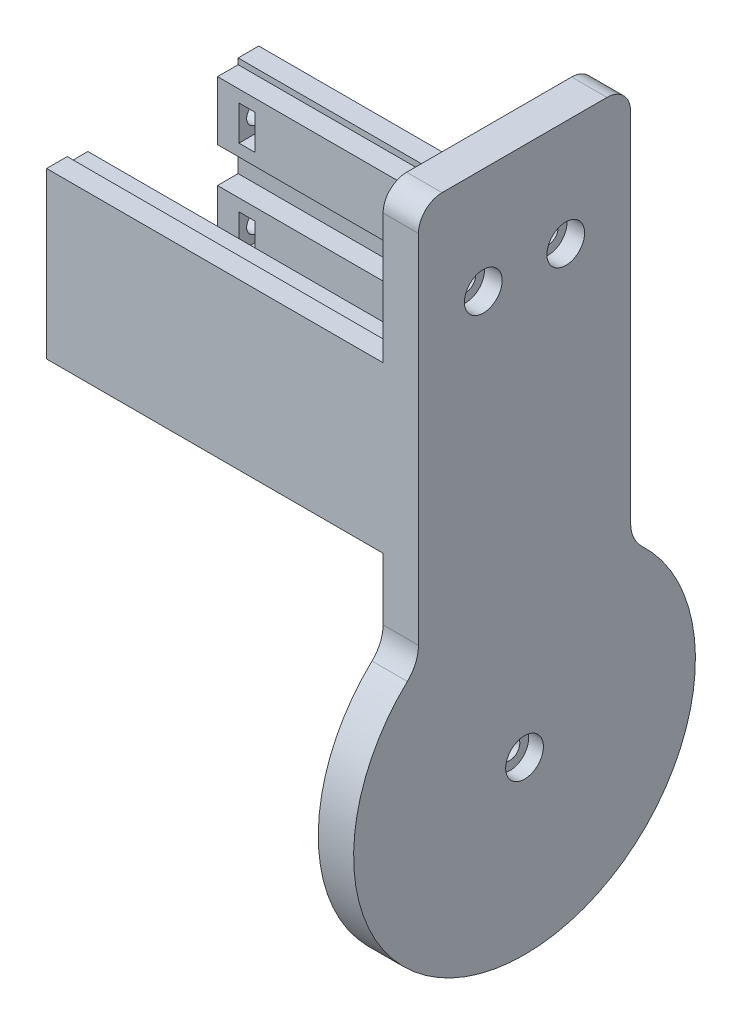
SolidWorks part; units mm, degrees
ref_plane "Front Plane" through (0, 0, 0) normal (0, 0, 1) x (1, 0, 0)
ref_plane "Top Plane" through (0, 0, 0) normal (0, 1, 0) x (1, 0, 0)
ref_plane "Right Plane" through (0, 0, 0) normal (1, 0, 0) x (0, 0, -1)
sketch "Sketch1" plane through (0, 0, 0) normal (1, 0, 0) x (0, 0, -1)
  line L0 (-32, 227.9755) -> (-32, 288.5)
  line L1 (-28, 292.5) -> (0, 292.5)
  line L2 (4, 288.5) -> (4, 227.9755)
  arc A0 (5.8857, 223.6083) -> (-33.8857, 223.6083) centre (-14, 202.5) cw
  arc A1 (-33.8857, 223.6083) -> (-32, 227.9755) centre (-38, 227.9755) ccw
  arc A2 (-32, 288.5) -> (-28, 292.5) centre (-28, 288.5) cw
  arc A3 (0, 292.5) -> (4, 288.5) centre (0, 288.5) cw
  arc A4 (4, 227.9755) -> (5.8857, 223.6083) centre (10, 227.9755) ccw
extrude "Plate D" add sketch "Sketch1" along normal blind 6 from offset 28.55
sketch "Sketch2" plane through (0, 0, 0) normal (1, 0, 0) x (0, 0, -1)
  line L0 (0.5, 238.5) -> (0.5, 266.5)
  line L1 (0.5, 266.5) -> (4, 266.5)
  line L2 (4, 266.5) -> (4, 238.5)
  line L3 (4, 238.5) -> (0.5, 238.5)
  line L4 (-28.5, 238.5) -> (-28.5, 266.5)
  line L5 (-28.5, 266.5) -> (-32, 266.5)
  line L6 (-32, 266.5) -> (-32, 238.5)
  line L7 (-32, 238.5) -> (-28.5, 238.5)
extrude "Box walls" add sketch "Sketch2" along normal blind 57.3 from offset 28.55 offset against normal yes
sketch "Sketch3" plane through (0, 0, 0) normal (1, 0, 0) x (0, 0, -1)
  line L0 (-3, 239.5) -> (-3, 249.5)
  line L1 (-3, 249.5) -> (0.5, 249.5)
  line L2 (0.5, 249.5) -> (0.5, 239.5)
  line L3 (0.5, 239.5) -> (-3, 239.5)
  line L4 (-25, 239.5) -> (-25, 249.5)
  line L5 (-25, 249.5) -> (-28.5, 249.5)
  line L6 (-28.5, 249.5) -> (-28.5, 239.5)
  line L7 (-28.5, 239.5) -> (-25, 239.5)
  line L8 (-3, 255.5) -> (-3, 265.5)
  line L9 (-3, 265.5) -> (0.5, 265.5)
  line L10 (0.5, 265.5) -> (0.5, 255.5)
  line L11 (0.5, 255.5) -> (-3, 255.5)
  line L12 (-25, 255.5) -> (-25, 265.5)
  line L13 (-25, 265.5) -> (-28.5, 265.5)
  line L14 (-28.5, 265.5) -> (-28.5, 255.5)
  line L15 (-28.5, 255.5) -> (-25, 255.5)
extrude "Wall bosses" add sketch "Sketch3" along normal blind 57.3 from offset 28.55 offset against normal yes
sketch "Sketch4" plane through (0, 0, 0) normal (1, 0, 0) x (0, 0, -1)
  line L0 (-18.4, 179.4) -> (-18.4, 225.6)
  line L1 (-9.6, 225.6) -> (-9.6, 179.4)
  arc A0 (-18.4, 225.6) -> (-9.6, 225.6) centre (-14, 225.6) cw
  arc A1 (-9.6, 179.4) -> (-18.4, 179.4) centre (-14, 179.4) cw
extrude "Horn pocket" cut sketch "Sketch4" along normal blind 2.5 from offset 28.35
sketch "Sketch5" plane through (0, 0, 0) normal (1, 0, 0) x (0, 0, -1)
  circle A0 centre (-14, 202.5) radius 1.7
  circle A1 centre (-7, 274.5) radius 1.7
  circle A2 centre (-21, 274.5) radius 1.7
extrude "Bolt holes" cut sketch "Sketch5" along normal blind 6.4 from offset 28.35
sketch "Sketch6" plane through (0, 0, 0) normal (1, 0, 0) x (0, 0, -1)
  circle A0 centre (-14, 202.5) radius 3.2
extrude "Hub counterbore" cut sketch "Sketch6" along normal blind 2.7 from offset 32.05
sketch "Sketch7" plane through (0, 0, 0) normal (1, 0, 0) x (0, 0, -1)
  circle A0 centre (-7, 274.5) radius 3.2
  circle A1 centre (-21, 274.5) radius 3.2
extrude "Head-mount counterbores" cut sketch "Sketch7" along normal blind 3.2 from offset 31.55
sketch "Sketch8" plane through (0, 0, 0) normal (1, 0, 0) x (0, 0, -1)
  circle A0 centre (0, 244.5) radius 1.7
  circle A1 centre (-28, 244.5) radius 1.7
  circle A2 centre (0, 260.5) radius 1.7
  circle A3 centre (-28, 260.5) radius 1.7
extrude "Cover bolt holes" cut sketch "Sketch8" along normal blind 10.2 from offset 28.75 offset against normal yes
sketch "Sketch9" plane through (0, 0, 0) normal (1, 0, 0) x (0, 0, -1)
  line L0 (-1.7032, 241.55) -> (1.7032, 241.55)
  line L1 (1.7032, 241.55) -> (3.4064, 244.5)
  line L2 (3.4064, 244.5) -> (1.7032, 247.45)
  line L3 (1.7032, 247.45) -> (-1.7032, 247.45)
  line L4 (-1.7032, 247.45) -> (-3.4, 247.45)
  line L5 (-3.4, 247.45) -> (-3.4, 241.55)
  line L6 (-3.4, 241.55) -> (-1.7032, 241.55)
  line L7 (-26.2968, 247.45) -> (-29.7032, 247.45)
  line L8 (-29.7032, 247.45) -> (-31.4064, 244.5)
  line L9 (-31.4064, 244.5) -> (-29.7032, 241.55)
  line L10 (-29.7032, 241.55) -> (-26.2968, 241.55)
  line L11 (-26.2968, 241.55) -> (-24.6, 241.55)
  line L12 (-24.6, 241.55) -> (-24.6, 247.45)
  line L13 (-24.6, 247.45) -> (-26.2968, 247.45)
  line L14 (-1.7032, 257.55) -> (1.7032, 257.55)
  line L15 (1.7032, 257.55) -> (3.4064, 260.5)
  line L16 (3.4064, 260.5) -> (1.7032, 263.45)
  line L17 (1.7032, 263.45) -> (-1.7032, 263.45)
  line L18 (-1.7032, 263.45) -> (-3.4, 263.45)
  line L19 (-3.4, 263.45) -> (-3.4, 257.55)
  line L20 (-3.4, 257.55) -> (-1.7032, 257.55)
  line L21 (-26.2968, 263.45) -> (-29.7032, 263.45)
  line L22 (-29.7032, 263.45) -> (-31.4064, 260.5)
  line L23 (-31.4064, 260.5) -> (-29.7032, 257.55)
  line L24 (-29.7032, 257.55) -> (-26.2968, 257.55)
  line L25 (-26.2968, 257.55) -> (-24.6, 257.55)
  line L26 (-24.6, 257.55) -> (-24.6, 263.45)
  line L27 (-24.6, 263.45) -> (-26.2968, 263.45)
extrude "Cover nut slots" cut sketch "Sketch9" along normal blind 2.7 from offset 24.9 offset against normal yes
